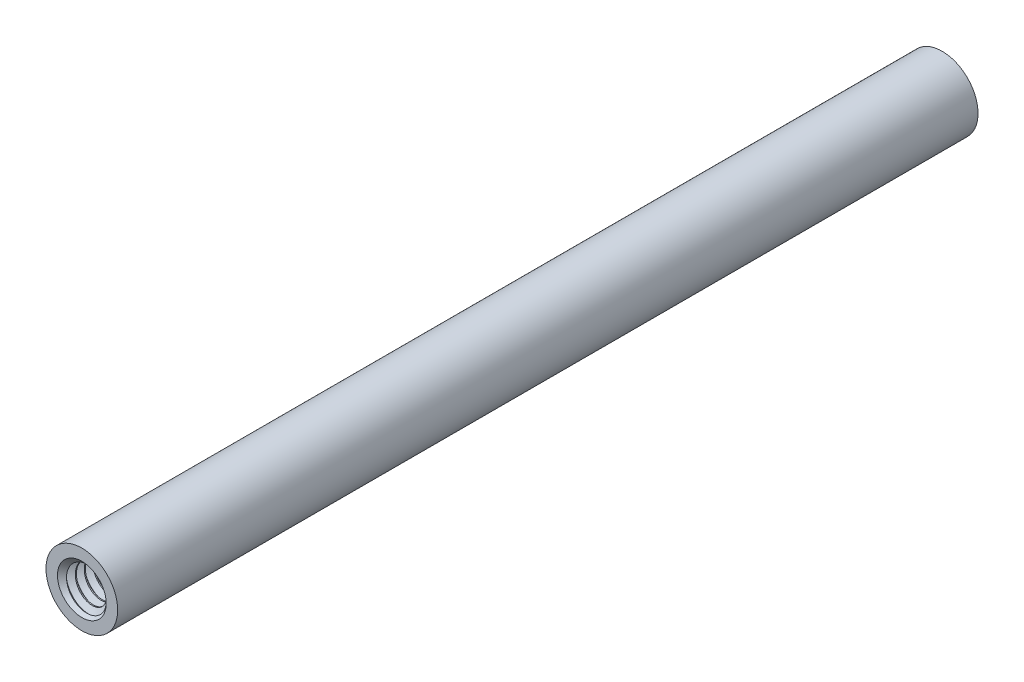
SolidWorks part; units mm, degrees
ref_plane "Front Plane" through (0, 0, 0) normal (0, 0, 1) x (1, 0, 0)
ref_plane "Top Plane" through (0, 0, 0) normal (0, 1, 0) x (1, 0, 0)
ref_plane "Right Plane" through (0, 0, 0) normal (1, 0, 0) x (0, 0, -1)
sketch "Sketch3" plane through (0, 0, 0) normal (1, 0, 0) x (0, 0, -1)
  line L0 (-38.1, 0) -> (38.1, 0) construction
  line L1 (0, 3.175) -> (0, -3.175) construction
  line L2 (-38.1, 2.0828) -> (-38.1, -2.0828) construction
  point P2 (26.9875, 0)
  point P3 (-26.9875, 0)
  dimension "Length" = 76.2
  dimension "Min Thread Length" = 11.1125
  dimension "D1" = 11.1125
  dimension "Thread Dia" = 4.1656
  dimension "OD" = 6.35
ref_axis "Axis1" through (0, 3.175, 0) along (0, -1, 0)
sketch "Sketch10" plane through (0, 0, 0) normal (1, 0, 0) x (0, 0, -1)
  line L0 (38.1, 2.0828) -> (26.9875, 2.0828)
  line L1 (-38.1, 2.0828) -> (-26.9875, 2.0828)
  line L2 (26.9875, 2.0828) -> (26.9875, -2.0828)
  line L3 (-38.1, -2.0828) -> (-26.9875, -2.0828)
  line L4 (-26.9875, 2.0828) -> (-26.9875, -2.0828)
  line L5 (26.9875, -2.0828) -> (38.1, -2.0828)
sketch "Sketch13" plane through (0, 0, 0) normal (0, 0, 1) x (1, 0, 0)
  circle A0 centre (0, 0) radius 2.0828
extrude "Boss-Extrude1" add sketch "Sketch13" against normal up to vertex (-26.9875 mm away) from vertex at 38.1 starting at point (0, 0, 38.1)
sketch "Sketch14" plane through (0, 0, 38.1) normal (0, 0, 1) x (1, 0, 0)
  circle A1 centre (0, 0) radius 2.0828
  circle A2 centre (0, 0) radius 2.0828
  dimension "D1" = 0
curve "Helix/Spiral2" pitch 0.7937 height 11.9062 turns 15 parameters "Pitch"=0.7937
sketch "Sketch15" plane through (0, 0, 0) normal (1, 0, 0) x (0, 0, -1)
  line L0 (-38.7945, 2.0828) -> (-38.1, 2.0828)
  line L1 (-38.7945, 2.0828) -> (-38.4969, 1.5672)
  line L2 (-38.4969, 1.5672) -> (-38.3977, 1.5672)
  line L3 (-38.3977, 1.5672) -> (-38.1, 2.0828)
  line L4 (-38.4473, 1.5672) -> (-38.4473, 2.0828) construction
  line L5 (-38.6457, 1.825) -> (-38.2488, 1.825) construction
  dimension "D1" = 60
  dimension "D2" = 0.0992
  dimension "D3" = 0.3969
sweep "Cut-Sweep1" cut profiles "Sketch15" path "Helix/Spiral2" align with end faces yes
sketch "Sketch16" plane through (0, 0, 38.1) normal (0, 0, 1) x (1, 0, 0)
  circle A2 centre (0, 0) radius 2.159
  circle A3 centre (0, 0) radius 2.159
  dimension "D1" = 0.0762
extrude "Boss-Extrude2" add sketch "Sketch16" against normal through all draft 45
pattern_circular "CirPattern1" count 2 over 180 about axis through (0, 3.175, 0) along (0, -1, 0) of bodies 113
sketch "Sketch1" plane through (0, 0, 0) normal (0, 0, 1) x (1, 0, 0)
  circle A1 centre (0, 0) radius 2.0828 construction
  circle A2 centre (0, 0) radius 3.175
extrude "Extrude1" add sketch "Sketch1" along normal up to vertex (38.1 mm away) and the other way up to vertex (38.1 mm away) up to point (0, 0, 38.1) other way up to point (0, 0, -38.1)
combine bodies "Combine1" operation type subtract main body 101 bodies to subtract 114 113
equation "\"D1@Sketch3\" = \"Min Thread Length@Sketch3\""
equation "\"D3@Helix/Spiral2\" = \"Min Thread Length@Sketch3\"+\"Pitch@Helix/Spiral2\""
equation "\"D2@Sketch15\" = \"Pitch@Helix/Spiral2\"*.125"
equation "\"D3@Sketch15\" = \"Pitch@Helix/Spiral2\"*.5"
